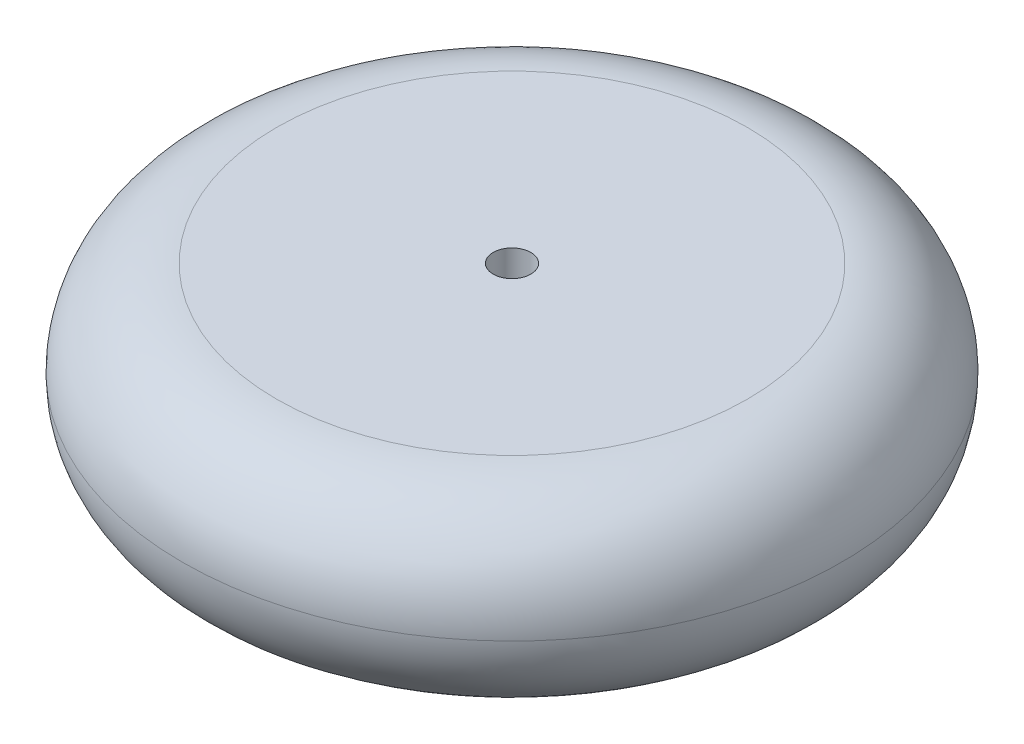
SolidWorks part; units mm, degrees
ref_plane "Front Plane" through (0, 0, 0) normal (0, 0, 1) x (1, 0, 0)
ref_plane "Top Plane" through (0, 0, 0) normal (0, 1, 0) x (1, 0, 0)
ref_plane "Right Plane" through (0, 0, 0) normal (1, 0, 0) x (0, 0, -1)
sketch "Sketch1" plane through (0, 0, 0) normal (0, 1, 0) x (1, 0, 0)
  circle A0 centre (0, 0) radius 7
  circle A1 centre (0, 0) radius 0.4
  dimension "D1" = 14
  dimension "D2" = 0.8
extrude "Boss-Extrude1" add sketch "Sketch1" along normal blind 4
fillet "Fillet1" radius 2 2 edges at (0, 0, 7) (0, 4, 7)
